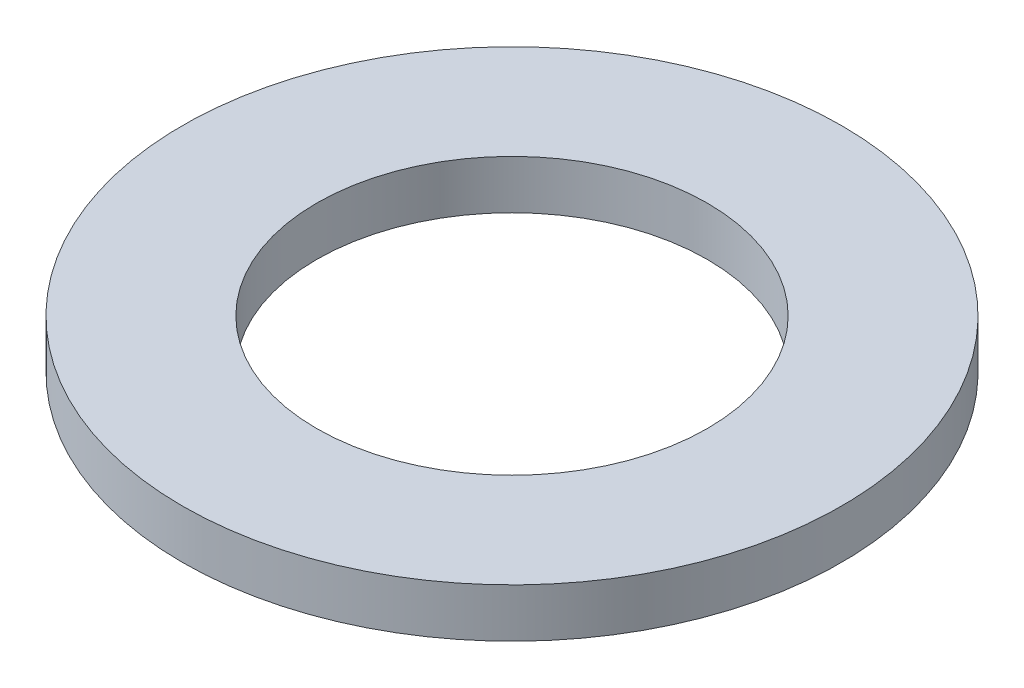
SolidWorks part; units mm, degrees
ref_plane "Front Plane" through (0, 0, 0) normal (0, 0, 1) x (1, 0, 0)
ref_plane "Top Plane" through (0, 0, 0) normal (0, 1, 0) x (1, 0, 0)
ref_plane "Right Plane" through (0, 0, 0) normal (1, 0, 0) x (0, 0, -1)
sketch "Sketch1" plane through (0, 0, 0) normal (0, 1, 0) x (1, 0, 0)
  circle A0 centre (0, 0) radius 67.5
  dimension "FLANGE_OD" = 135
extrude "Boss-Extrude1" add sketch "Sketch1" along normal blind 10
sketch "Sketch2" plane through (0, 0, 0) normal (0, 1, 0) x (1, 0, 0)
  circle A0 centre (0, 0) radius 40
  dimension "BORE_D" = 80
extrude "Cut-Extrude1" cut sketch "Sketch2" along normal through all
sketch "Sketch3" plane through (0, 10, 0) normal (0, 1, 0) x (1, 0, 0)
  circle A0 centre (0, 0) radius 25.5896 construction
  circle A1 centre (-25.5896, 0) radius 2.7216
  dimension "BOLT_D" = 5.4433
  dimension "BOLT_PCD" = 51.1793
extrude "Cut-Extrude2" cut sketch "Sketch3" against normal blind 8.7305 rebuild error yes
pattern_circular "CirPattern1" count 4 over 360 rebuild error yes
